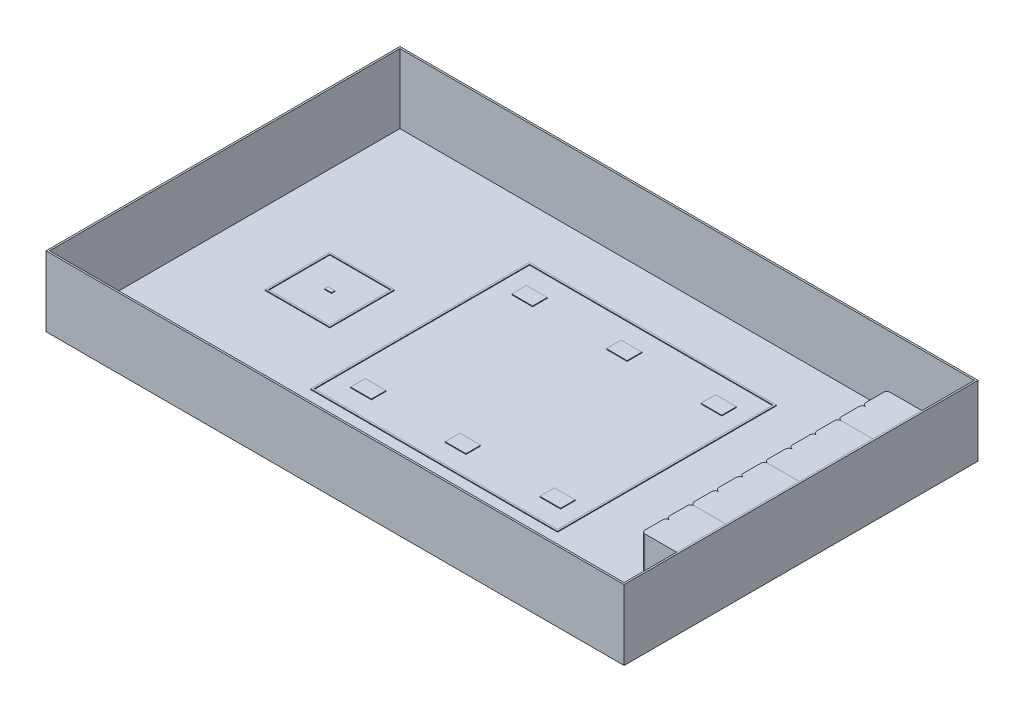
SolidWorks part; units mm, degrees
ref_plane "Front Plane" through (0, 0, 0) normal (0, 0, 1) x (1, 0, 0)
ref_plane "Top Plane" through (0, 0, 0) normal (0, 1, 0) x (1, 0, 0)
ref_plane "Right Plane" through (0, 0, 0) normal (1, 0, 0) x (0, 0, -1)
sketch "Sketch1" plane through (0, 0, 0) normal (0, 1, 0) x (1, 0, 0)
  line L0 (0, 0) -> (2600, 0) construction
  line L1 (-450, -450) -> (450, -450)
  line L2 (-450, -450) -> (-450, 450)
  line L3 (-450, 450) -> (450, 450)
  line L4 (450, -450) -> (450, 450)
  line L5 (-450, -450) -> (450, 450) construction
  line L6 (-450, 450) -> (450, -450) construction
  line L7 (6700, -2500) -> (-1500, -2500)
  line L8 (6700, -2500) -> (6700, 2500)
  line L9 (6700, 2500) -> (-1500, 2500)
  line L10 (-1500, -2500) -> (-1500, 2500)
  line L11 (6700, -2500) -> (-1500, 2500) construction
  line L12 (6700, 2500) -> (-1500, -2500) construction
  line L14 (1500, -950) -> (4200, -950) construction
  line L15 (1500, -950) -> (1500, 1350) construction
  line L16 (1500, 1350) -> (4200, 1350) construction
  line L17 (4200, -950) -> (4200, 1350) construction
  line L18 (-50, -25) -> (50, -25)
  line L19 (-50, -25) -> (-50, 25)
  line L20 (-50, 25) -> (50, 25)
  line L21 (50, -25) -> (50, 25)
  line L22 (-50, -25) -> (50, 25) construction
  line L23 (-50, 25) -> (50, -25) construction
  line L24 (1351.5, 1245) -> (1648.5, 1245)
  line L25 (1351.5, 1245) -> (1351.5, 1455)
  line L26 (1351.5, 1455) -> (1648.5, 1455)
  line L27 (1648.5, 1245) -> (1648.5, 1455)
  line L28 (1351.5, 1245) -> (1648.5, 1455) construction
  line L29 (1351.5, 1455) -> (1648.5, 1245) construction
  line L33 (2701.5, 1245) -> (2998.5, 1245)
  line L34 (2701.5, 1245) -> (2701.5, 1455)
  line L35 (2701.5, 1455) -> (2998.5, 1455)
  line L36 (2998.5, 1245) -> (2998.5, 1455)
  line L37 (2701.5, 1245) -> (2998.5, 1455) construction
  line L38 (2701.5, 1455) -> (2998.5, 1245) construction
  line L39 (4051.5, 1245) -> (4348.5, 1245)
  line L40 (4051.5, 1245) -> (4051.5, 1455)
  line L41 (4051.5, 1455) -> (4348.5, 1455)
  line L42 (4348.5, 1245) -> (4348.5, 1455)
  line L43 (4051.5, 1245) -> (4348.5, 1455) construction
  line L44 (4051.5, 1455) -> (4348.5, 1245) construction
  line L45 (1351.5, -1055) -> (1648.5, -1055)
  line L46 (1351.5, -1055) -> (1351.5, -845)
  line L47 (1351.5, -845) -> (1648.5, -845)
  line L48 (1648.5, -1055) -> (1648.5, -845)
  line L49 (1351.5, -1055) -> (1648.5, -845) construction
  line L50 (1351.5, -845) -> (1648.5, -1055) construction
  line L51 (2701.5, -1055) -> (2998.5, -1055)
  line L52 (2701.5, -1055) -> (2701.5, -845)
  line L53 (2701.5, -845) -> (2998.5, -845)
  line L54 (2998.5, -1055) -> (2998.5, -845)
  line L55 (2701.5, -1055) -> (2998.5, -845) construction
  line L56 (2701.5, -845) -> (2998.5, -1055) construction
  line L57 (4051.5, -1055) -> (4348.5, -1055)
  line L58 (4051.5, -1055) -> (4051.5, -845)
  line L59 (4051.5, -845) -> (4348.5, -845)
  line L60 (4348.5, -1055) -> (4348.5, -845)
  line L61 (4051.5, -1055) -> (4348.5, -845) construction
  line L62 (4051.5, -845) -> (4348.5, -1055) construction
  line L63 (1100, -1350) -> (4600, -1350)
  line L64 (4600, -1350) -> (4600, 1750)
  line L65 (1100, 1750) -> (4600, 1750)
  line L66 (1100, -1350) -> (1100, 1750)
  point P0 (0, 0)
  point P6 (2600, 0)
  point P17 (2850, -950)
  point P18 (2850, 1350)
  point P31 (4200, 1350)
  point P36 (6700, 0)
  point P37 (1500, -950)
  point P43 (2850, -950)
  point P49 (4200, -950)
  line B0 (6700, 1750) -> (6250, 1750)
  line B1 (6700, 1750) -> (6700, 1400)
  line B2 (6700, 1400) -> (6250, 1400)
  line B3 (6200, 1700) -> (6200, 1450)
  arc B4 (6250, 1400) -> (6200, 1450) centre (6250, 1450) cw
  arc B5 (6250, 1750) -> (6200, 1700) centre (6250, 1700) ccw
  line B6 (6700, 1400) -> (6250, 1400)
  line B7 (6700, 1400) -> (6700, 1050)
  line B8 (6700, 1050) -> (6250, 1050)
  line B9 (6200, 1350) -> (6200, 1100)
  arc B10 (6250, 1050) -> (6200, 1100) centre (6250, 1100) cw
  arc B11 (6250, 1400) -> (6200, 1350) centre (6250, 1350) ccw
  line B12 (6700, 1050) -> (6250, 1050)
  line B13 (6700, 1050) -> (6700, 700)
  line B14 (6700, 700) -> (6250, 700)
  line B15 (6200, 1000) -> (6200, 750)
  arc B16 (6250, 700) -> (6200, 750) centre (6250, 750) cw
  arc B17 (6250, 1050) -> (6200, 1000) centre (6250, 1000) ccw
  line B18 (6700, 700) -> (6250, 700)
  line B19 (6700, 700) -> (6700, 350)
  line B20 (6700, 350) -> (6250, 350)
  line B21 (6200, 650) -> (6200, 400)
  arc B22 (6250, 350) -> (6200, 400) centre (6250, 400) cw
  arc B23 (6250, 700) -> (6200, 650) centre (6250, 650) ccw
  line B24 (6700, 350) -> (6250, 350)
  line B25 (6700, 350) -> (6700, 0)
  line B26 (6700, 0) -> (6250, 0)
  line B27 (6200, 300) -> (6200, 50)
  arc B28 (6250, 0) -> (6200, 50) centre (6250, 50) cw
  arc B29 (6250, 350) -> (6200, 300) centre (6250, 300) ccw
  line B30 (6700, 0) -> (6250, 0)
  line B31 (6700, 0) -> (6700, -350)
  line B32 (6700, -350) -> (6250, -350)
  line B33 (6200, -50) -> (6200, -300)
  arc B34 (6250, -350) -> (6200, -300) centre (6250, -300) cw
  arc B35 (6250, 0) -> (6200, -50) centre (6250, -50) ccw
  line B36 (6700, -350) -> (6250, -350)
  line B37 (6700, -350) -> (6700, -700)
  line B38 (6700, -700) -> (6250, -700)
  line B39 (6200, -400) -> (6200, -650)
  arc B40 (6250, -700) -> (6200, -650) centre (6250, -650) cw
  arc B41 (6250, -350) -> (6200, -400) centre (6250, -400) ccw
  line B42 (6700, -700) -> (6250, -700)
  line B43 (6700, -700) -> (6700, -1050)
  line B44 (6700, -1050) -> (6250, -1050)
  line B45 (6200, -750) -> (6200, -1000)
  arc B46 (6250, -1050) -> (6200, -1000) centre (6250, -1000) cw
  arc B47 (6250, -700) -> (6200, -750) centre (6250, -750) ccw
  line B48 (6700, -1050) -> (6250, -1050)
  line B49 (6700, -1050) -> (6700, -1400)
  line B50 (6700, -1400) -> (6250, -1400)
  line B51 (6200, -1100) -> (6200, -1350)
  arc B52 (6250, -1400) -> (6200, -1350) centre (6250, -1350) cw
  arc B53 (6250, -1050) -> (6200, -1100) centre (6250, -1100) ccw
  line B54 (6700, -1400) -> (6250, -1400)
  line B55 (6700, -1400) -> (6700, -1750)
  line B56 (6700, -1750) -> (6250, -1750)
  line B57 (6200, -1450) -> (6200, -1700)
  arc B58 (6250, -1750) -> (6200, -1700) centre (6250, -1700) cw
  arc B59 (6250, -1400) -> (6200, -1450) centre (6250, -1450) ccw
  dimension "D23" = 10
  dimension "D1" = 900
  dimension "D2" = 1500
  dimension "D3" = 2500
  dimension "D4" = 950
  dimension "D5" = 1350
  dimension "D6" = 1500
  dimension "D7" = 2700
  dimension "D8" = 2500
  dimension "D9" = 50
  dimension "D10" = 100
  dimension "D11" = 297
  dimension "D12" = 210
  dimension "D13" = 297
  dimension "D14" = 210
  dimension "D15" = 297
  dimension "D16" = 210
  dimension "D17" = 297
  dimension "D18" = 210
  dimension "D19" = 297
  dimension "D20" = 210
  dimension "D21" = 297
  dimension "D22" = 210
  dimension "D24" = 400
sketch_block_instance "Block2-1"
sketch_block "Block2" parameters "D1"=50, "D2"=350
sketch_block_instance "Block2-2"
sketch_block_instance "Block2-3"
sketch_block_instance "Block2-4"
sketch_block_instance "Block2-5"
sketch_block_instance "Block2-6"
sketch_block_instance "Block2-7"
sketch_block_instance "Block2-8"
sketch_block_instance "Block2-9"
sketch_block_instance "Block2-10"
extrude "Boss-Extrude1" add sketch "Sketch1" along normal blind 10 contours L1 L4 L3 L2 | L10 L7 L8 L9 L4 L1 L2 L3 | L18 L21 L20 L19 | L45 L48 L47 L46 | L51 L54 L53 L52 | L57 L60 L59 L58 | L39 L42 L41 L40 | L33 L36 L35 L34 | L24 L27 L26 L25 | B50 B59 B57 B58 B56 L8 | B44 B53 B51 B52 B50 L8 | B38 B47 B45 B46 B44 L8 | B32 B41 B39 B40 B38 L8 | B26 B35 B33 B34 B32 L8 | B20 B29 B27 B28 B26 L8 | B14 B23 B21 B22 B20 L8 | B0 B5 B3 B4 B2 L8 | B2 B11 B9 B10 B8 L8 | B8 B17 B15 B16 B14 L8 | L66 L63 L64 L65 L60 L57 L58 L59 L54 L51 L52 L53 L48 L45 L46 L47 L42 L39 L40 L41 L36 L33 L34 L35 L27 L24 L25 L26 region at (-437.2721, 0, 0) region at (2600, 0, 2403.9583) region at (6451.4734, 0, 1575) region at (6451.4734, 0, 1225) region at (6451.4734, 0, 875) region at (6451.4734, 0, -1575) region at (6451.4734, 0, 525) region at (6451.4734, 0, -1225) region at (6451.4734, 0, 175) region at (6451.4734, 0, -875) region at (6451.4734, 0, -175) region at (6451.4734, 0, -525) region at (0, 0, 0) region at (1500, 0, -1350) region at (2850, 0, -1350) region at (4200, 0, -1350) region at (1500, 0, 950) region at (2850, 0, 950) region at (4200, 0, 950) region at (2850, 0, -200)
extrude "Extrude-Thin1" add sketch "Sketch1<4>" along normal blind 10 and the other way blind 10 from surface separate body thin contours L2 L3 L4 L1 starting at face at (2600, 10, 0) thin type mid plane wall 25
sketch "Sketch1<4>" plane through (0, 0, 0) normal (0, 1, 0) x (1, 0, 0) same geometry as "Sketch1"
extrude "Boss-Extrude3" add sketch "Sketch1<5>" along normal blind 10 from surface separate body contours L18 L21 L20 L19 region at (0, 0, 0) starting at face at (2600, 10, 0)
sketch "Sketch1<5>" plane through (0, 0, 0) normal (0, 1, 0) x (1, 0, 0) same geometry as "Sketch1"
extrude "Extrude-Thin2" add sketch "Sketch1<6>" along normal blind 1000 separate body thin contours L7 L10 L9 L8 thin type one direction wall 25
sketch "Sketch1<6>" plane through (0, 0, 0) normal (0, 1, 0) x (1, 0, 0) same geometry as "Sketch1"
extrude "Boss-Extrude4" add sketch "Sketch1<7>" along normal blind 10 from surface separate body contours L51 L54 L53 L52 | L45 L48 L47 L46 | L24 L27 L26 L25 | L33 L36 L35 L34 | L39 L42 L41 L40 | L57 L60 L59 L58 region at (1500, 0, -1350) region at (2850, 0, -1350) region at (4200, 0, -1350) region at (1500, 0, 950) region at (2850, 0, 950) region at (4200, 0, 950) starting at face at (0, 10, 0)
sketch "Sketch1<7>" plane through (0, 0, 0) normal (0, 1, 0) x (1, 0, 0) same geometry as "Sketch1"
extrude "Boss-Extrude6" add sketch "Sketch1<8>" along normal blind 990 from surface separate body contours B0 B5 B3 B4 B2 L8 | B2 B11 B9 B10 B8 L8 region at (6451.4734, 0, -1575) region at (6451.4734, 0, -1225) starting at face at (2600, 10, 0)
sketch "Sketch1<8>" plane through (0, 0, 0) normal (0, 1, 0) x (1, 0, 0) same geometry as "Sketch1"
extrude "Boss-Extrude7" add sketch "Sketch1<9>" along normal blind 990 from surface separate body contours B8 B17 B15 B16 B14 L8 | B14 B23 B21 B22 B20 L8 | B20 B29 B27 B28 B26 L8 region at (6451.4734, 0, -875) region at (6451.4734, 0, -175) region at (6451.4734, 0, -525) starting at face at (2600, 10, 0)
sketch "Sketch1<9>" plane through (0, 0, 0) normal (0, 1, 0) x (1, 0, 0) same geometry as "Sketch1"
extrude "Boss-Extrude8" add sketch "Sketch1<10>" along normal blind 990 from surface separate body contours B32 B41 B39 B40 B38 L8 | B26 B35 B33 B34 B32 L8 | B38 B47 B45 B46 B44 L8 region at (6451.4734, 0, 875) region at (6451.4734, 0, 525) region at (6451.4734, 0, 175) starting at face at (2600, 10, 0)
sketch "Sketch1<10>" plane through (0, 0, 0) normal (0, 1, 0) x (1, 0, 0) same geometry as "Sketch1"
extrude "Boss-Extrude9" add sketch "Sketch1<11>" along normal blind 990 from surface separate body contours B44 B53 B51 B52 B50 L8 | B50 B59 B57 B58 B56 L8 region at (6451.4734, 0, 1575) region at (6451.4734, 0, 1225) starting at face at (2600, 10, 0)
sketch "Sketch1<11>" plane through (0, 0, 0) normal (0, 1, 0) x (1, 0, 0) same geometry as "Sketch1"
extrude "Extrude-Thin3" add sketch "Sketch1<12>" along normal blind 10 from surface separate body thin contours L66 L65 L64 L63 starting at face at (2600, 10, 0) thin type mid plane wall 25
sketch "Sketch1<12>" plane through (0, 0, 0) normal (0, 1, 0) x (1, 0, 0) same geometry as "Sketch1"
